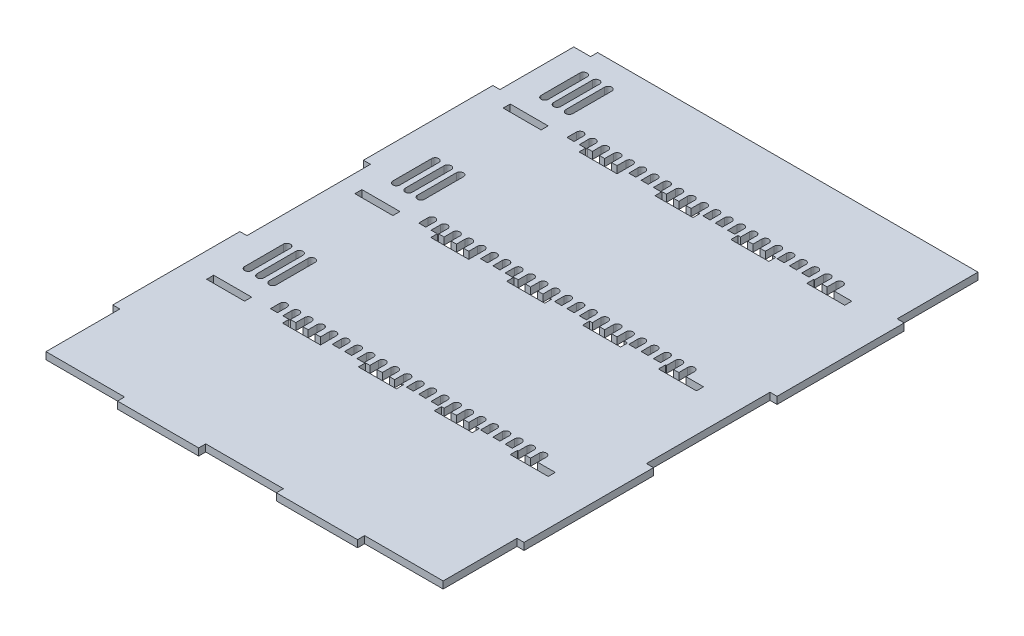
SolidWorks part; units mm, degrees
ref_plane "Front Plane" through (0, 0, 0) normal (0, 0, 1) x (1, 0, 0)
ref_plane "Top Plane" through (0, 0, 0) normal (0, 1, 0) x (1, 0, 0)
ref_plane "Right Plane" through (0, 0, 0) normal (1, 0, 0) x (0, 0, -1)
sketch "Sketch1" plane through (0, 0, 0) normal (0, 1, 0) x (1, 0, 0)
  line L1 (0, 0) -> (233, 0)
  line L2 (0, 0) -> (0, 307)
  line L3 (0, 307) -> (233, 307)
  line L4 (233, 0) -> (233, 307)
  dimension "D1" = 233
  dimension "D2" = 307
extrude "Boss-Extrude1" add sketch "Sketch1" along normal blind 4
sketch "Sketch2" plane through (0, 4, 0) normal (0, 1, 0) x (1, 0, 0)
  line L1 (0, 307) -> (4, 307)
  line L2 (0, 307) -> (0, 261.1667)
  line L3 (0, 261.1667) -> (4, 261.1667)
  line L4 (4, 307) -> (4, 261.1667)
  line L5 (0, 0) -> (4, 0)
  line L6 (0, 0) -> (0, 45.8333)
  line L7 (0, 45.8333) -> (4, 45.8333)
  line L8 (4, 0) -> (4, 45.8333)
  line L9 (233, 0) -> (233, 307) construction
  line L10 (0, 0) -> (233, 0) construction
  line L11 (4, 307) -> (13.5, 307)
  line L12 (4, 307) -> (4, 303)
  line L13 (4, 303) -> (13.5, 303)
  line L14 (13.5, 307) -> (13.5, 303)
  line L15 (94.5, 0) -> (94.5, 4)
  line L16 (4, 0) -> (48.5, 0)
  line L17 (4, 0) -> (4, 4)
  line L18 (4, 4) -> (48.5, 4)
  line L19 (48.5, 0) -> (48.5, 4)
  line L20 (94.5, 0) -> (138.5, 0)
  line L21 (138.5, 0) -> (138.5, 4)
  line L22 (94.5, 4) -> (138.5, 4)
  line L23 (184.5, 0) -> (184.5, 4)
  line L24 (184.5, 0) -> (229, 0)
  line L26 (184.5, 4) -> (229, 4)
  line L27 (229, 307) -> (229, 261.1667)
  line L28 (229, 307) -> (233, 307)
  line L29 (233, 307) -> (233, 261.1667)
  line L30 (229, 261.1667) -> (233, 261.1667)
  line L31 (229, 0) -> (229, 45.8333)
  line L32 (229, 0) -> (233, 0)
  line L33 (233, 0) -> (233, 45.8333)
  line L34 (229, 45.8333) -> (233, 45.8333)
  line M15 (0, 307) -> (0, 0)
  line M16 (0, 0) -> (233, 0)
  line M18 (233, 307) -> (0, 307)
  dimension "D1" = 45.8333
  dimension "D2" = 45.8333
  dimension "D3" = 4
  dimension "D4" = 9.5
  dimension "D5" = 4
  dimension "D6" = 44.5
  dimension "D7" = 4
  dimension "D10" = 46
  dimension "D8" = 44
  dimension "D11" = 46
  dimension "D9" = 2
extrude "Cut-Extrude1" cut sketch "Sketch2" against normal blind 4 contours L4 L3 M18 M15 | L14 L4 L13 M18 | L8 L7 M16 M15 | L26 L23 M16 | L17 L18 L19 L16 | L22 L21 L20 L15 | L31 L34 L33 L32 | L29 L30 L27 L28 region at (206.75, 4, -2) region at (2, 4, -22.9167) region at (2, 4, -284.0833) region at (8.75, 4, -305)
sketch "Sketch3" plane through (0, 0, 0) normal (0, -1, 0) x (1, 0, 0)
  line L7 (207.5, -253) -> (186, -253)
  line L8 (207.5, -253) -> (207.5, -257)
  line L9 (207.5, -257) -> (186, -257)
  line L10 (186, -253) -> (186, -257)
  line L12 (164.5, -253) -> (164.5, -257)
  line L13 (164.5, -253) -> (143, -253)
  line L14 (143, -253) -> (143, -257)
  line L15 (164.5, -257) -> (143, -257)
  line L16 (121.5, -253) -> (121.5, -257)
  line L17 (121.5, -253) -> (100, -253)
  line L18 (100, -253) -> (100, -257)
  line L19 (121.5, -257) -> (100, -257)
  line L20 (78.5, -253) -> (78.5, -257)
  line L21 (78.5, -253) -> (57, -253)
  line L22 (57, -253) -> (57, -257)
  line L23 (78.5, -257) -> (57, -257)
  line L24 (35.5, -253) -> (35.5, -257)
  line L25 (35.5, -253) -> (14, -253)
  line L26 (14, -253) -> (14, -257)
  line L27 (35.5, -257) -> (14, -257)
  line L106 (229, -307) -> (13.5, -307) construction
  line L107 (35.5, -169) -> (35.5, -173)
  line L108 (35.5, -173) -> (14, -173)
  line L109 (14, -169) -> (14, -173)
  line L110 (35.5, -169) -> (14, -169)
  line L111 (78.5, -169) -> (78.5, -173)
  line L112 (78.5, -173) -> (57, -173)
  line L113 (57, -169) -> (57, -173)
  line L114 (78.5, -169) -> (57, -169)
  line L115 (121.5, -169) -> (121.5, -173)
  line L116 (121.5, -173) -> (100, -173)
  line L117 (100, -169) -> (100, -173)
  line L118 (121.5, -169) -> (100, -169)
  line L119 (164.5, -169) -> (164.5, -173)
  line L120 (164.5, -173) -> (143, -173)
  line L121 (143, -169) -> (143, -173)
  line L122 (164.5, -169) -> (143, -169)
  line L123 (207.5, -169) -> (207.5, -173)
  line L124 (207.5, -169) -> (186, -169)
  line L125 (186, -169) -> (186, -173)
  line L126 (207.5, -173) -> (186, -173)
  line L127 (35.5, -85) -> (35.5, -89)
  line L128 (35.5, -89) -> (14, -89)
  line L129 (14, -85) -> (14, -89)
  line L130 (35.5, -85) -> (14, -85)
  line L131 (78.5, -85) -> (78.5, -89)
  line L132 (78.5, -89) -> (57, -89)
  line L133 (57, -85) -> (57, -89)
  line L134 (78.5, -85) -> (57, -85)
  line L135 (121.5, -85) -> (121.5, -89)
  line L136 (121.5, -89) -> (100, -89)
  line L137 (100, -85) -> (100, -89)
  line L138 (121.5, -85) -> (100, -85)
  line L139 (164.5, -85) -> (164.5, -89)
  line L140 (164.5, -89) -> (143, -89)
  line L141 (143, -85) -> (143, -89)
  line L142 (164.5, -85) -> (143, -85)
  line L143 (207.5, -85) -> (207.5, -89)
  line L144 (207.5, -85) -> (186, -85)
  line L145 (186, -85) -> (186, -89)
  line L146 (207.5, -89) -> (186, -89)
  dimension "D1" = 50
  dimension "D2" = 21.5
  dimension "D3" = 4
  dimension "D5" = 5
extrude "Cut-Extrude2" cut sketch "Sketch3" against normal blind 4
sketch "Sketch4" plane through (0, 4, 0) normal (0, 1, 0) x (1, 0, 0)
  line L0 (0, 261.1667) -> (0, 45.8333) construction
  line L1 (0, 187.8333) -> (4, 187.8333)
  line L2 (0, 187.8333) -> (0, 117.8333)
  line L3 (0, 117.8333) -> (4, 117.8333)
  line L4 (4, 187.8333) -> (4, 117.8333)
  line L5 (0, 45.8333) -> (4, 45.8333) construction
  point P6 (4, 152.8333)
  dimension "D1" = 4
  dimension "D2" = 70
  dimension "D3" = 107
extrude "Cut-Extrude3" cut sketch "Sketch4" against normal blind 4
sketch "Sketch5" plane through (0, 4, 0) normal (0, 1, 0) x (1, 0, 0)
  line L0 (233, 45.8333) -> (233, 261.1667) construction
  line L1 (233, 189.1667) -> (229, 189.1667)
  line L2 (233, 189.1667) -> (233, 119.1667)
  line L3 (233, 119.1667) -> (229, 119.1667)
  line L4 (229, 189.1667) -> (229, 119.1667)
  line L5 (229, 261.1667) -> (233, 261.1667) construction
  point P6 (233, 154.1667)
  dimension "D1" = 4
  dimension "D2" = 70
  dimension "D3" = 107
extrude "Cut-Extrude4" cut sketch "Sketch5" against normal blind 4
sketch "Sketch6" plane through (0, 4, 0) normal (0, 1, 0) x (1, 0, 0)
  line L0 (20.5, 292) -> (20.5, 270) construction
  line L1 (22.5, 292) -> (22.5, 270)
  line L2 (18.5, 292) -> (18.5, 270)
  line L4 (4, 303) -> (13.5, 303) construction
  line L11 (13.5, 307) -> (13.5, 303) construction
  line L17 (109.5011, 256.6579) -> (113.5011, 256.6579)
  line L18 (25.5402, 292) -> (25.5402, 270)
  line L21 (29.5402, 292) -> (29.5402, 270)
  line L22 (27.5402, 292) -> (27.5402, 270) construction
  line L23 (34.4609, 292) -> (34.4609, 270) construction
  line L24 (36.4609, 292) -> (36.4609, 270)
  line L25 (32.4609, 292) -> (32.4609, 270)
  line L26 (102.5011, 261.9985) -> (102.5011, 256.6579)
  line L27 (111.5011, 261.9985) -> (111.5011, 258.9985) construction
  line L29 (113.5011, 261.9985) -> (113.5011, 256.6579)
  line L30 (109.5011, 261.9985) -> (109.5011, 256.6579)
  line L31 (102.5011, 256.6579) -> (106.5011, 256.6579)
  line L32 (106.5011, 261.9985) -> (106.5011, 256.6579)
  line L33 (95.5011, 261.9985) -> (95.5011, 256.6579)
  line L34 (95.5011, 256.6579) -> (99.5011, 256.6579)
  line L35 (99.5011, 261.9985) -> (99.5011, 256.6579)
  line L36 (88.5011, 261.9985) -> (88.5011, 256.6579)
  line L37 (88.5011, 256.6579) -> (92.5011, 256.6579)
  line L38 (92.5011, 261.9985) -> (92.5011, 256.6579)
  line L39 (81.5011, 261.9985) -> (81.5011, 256.6579)
  line L40 (81.5011, 256.6579) -> (85.5011, 256.6579)
  line L41 (85.5011, 261.9985) -> (85.5011, 256.6579)
  line L42 (74.5011, 261.9985) -> (74.5011, 256.6579)
  line L43 (74.5011, 256.6579) -> (78.5011, 256.6579)
  line L44 (78.5011, 261.9985) -> (78.5011, 256.6579)
  line L45 (67.5011, 261.9985) -> (67.5011, 256.6579)
  line L46 (67.5011, 256.6579) -> (71.5011, 256.6579)
  line L47 (71.5011, 261.9985) -> (71.5011, 256.6579)
  line L48 (60.5011, 261.9985) -> (60.5011, 256.6579)
  line L49 (60.5011, 256.6579) -> (64.5011, 256.6579)
  line L50 (64.5011, 261.9985) -> (64.5011, 256.6579)
  line L51 (53.5011, 261.9985) -> (53.5011, 256.6579)
  line L52 (53.5011, 256.6579) -> (57.5011, 256.6579)
  line L53 (57.5011, 261.9985) -> (57.5011, 256.6579)
  line L54 (116.5011, 261.9985) -> (116.5011, 256.6579)
  line L55 (116.5011, 256.6579) -> (120.5011, 256.6579)
  line L56 (120.5011, 261.9985) -> (120.5011, 256.6579)
  line L57 (123.5011, 261.9985) -> (123.5011, 256.6579)
  line L58 (123.5011, 256.6579) -> (127.5011, 256.6579)
  line L59 (127.5011, 261.9985) -> (127.5011, 256.6579)
  line L60 (130.5011, 261.9985) -> (130.5011, 256.6579)
  line L61 (130.5011, 256.6579) -> (134.5011, 256.6579)
  line L62 (134.5011, 261.9985) -> (134.5011, 256.6579)
  line L63 (137.5011, 261.9985) -> (137.5011, 256.6579)
  line L64 (137.5011, 256.6579) -> (141.5011, 256.6579)
  line L65 (141.5011, 261.9985) -> (141.5011, 256.6579)
  line L66 (144.5011, 261.9985) -> (144.5011, 256.6579)
  line L67 (144.5011, 256.6579) -> (148.5011, 256.6579)
  line L68 (148.5011, 261.9985) -> (148.5011, 256.6579)
  line L69 (151.5011, 261.9985) -> (151.5011, 256.6579)
  line L70 (151.5011, 256.6579) -> (155.5011, 256.6579)
  line L71 (155.5011, 261.9985) -> (155.5011, 256.6579)
  line L72 (158.5011, 261.9985) -> (158.5011, 256.6579)
  line L73 (158.5011, 256.6579) -> (162.5011, 256.6579)
  line L74 (162.5011, 261.9985) -> (162.5011, 256.6579)
  line L75 (165.5011, 261.9985) -> (165.5011, 256.6579)
  line L76 (165.5011, 256.6579) -> (169.5011, 256.6579)
  line L77 (169.5011, 261.9985) -> (169.5011, 256.6579)
  line L78 (172.5011, 261.9985) -> (172.5011, 256.6579)
  line L79 (172.5011, 256.6579) -> (176.5011, 256.6579)
  line L80 (176.5011, 261.9985) -> (176.5011, 256.6579)
  line L81 (179.5011, 261.9985) -> (179.5011, 256.6579)
  line L82 (179.5011, 256.6579) -> (183.5011, 256.6579)
  line L83 (183.5011, 261.9985) -> (183.5011, 256.6579)
  line L84 (186.5011, 261.9985) -> (186.5011, 256.6579)
  line L85 (186.5011, 256.6579) -> (190.5011, 256.6579)
  line L86 (190.5011, 261.9985) -> (190.5011, 256.6579)
  line L87 (46.5011, 261.9985) -> (46.5011, 256.6579)
  line L88 (46.5011, 256.6579) -> (50.5011, 256.6579)
  line L89 (50.5011, 261.9985) -> (50.5011, 256.6579)
  line L90 (193.5011, 261.9985) -> (193.5011, 256.6579)
  line L91 (193.5011, 256.6579) -> (197.5011, 256.6579)
  line L92 (197.5011, 261.9985) -> (197.5011, 256.6579)
  arc A0 (22.5, 292) -> (18.5, 292) centre (20.5, 292) ccw
  arc A1 (18.5, 270) -> (22.5, 270) centre (20.5, 270) ccw
  arc A14 (29.5402, 292) -> (25.5402, 292) centre (27.5402, 292) ccw
  arc A15 (25.5402, 270) -> (29.5402, 270) centre (27.5402, 270) ccw
  arc A16 (36.4609, 292) -> (32.4609, 292) centre (34.4609, 292) ccw
  arc A17 (32.4609, 270) -> (36.4609, 270) centre (34.4609, 270) ccw
  arc A18 (113.5011, 261.9985) -> (109.5011, 261.9985) centre (111.5011, 261.9985) ccw
  arc A20 (106.5011, 261.9985) -> (102.5011, 261.9985) centre (104.5011, 261.9985) ccw
  arc A21 (99.5011, 261.9985) -> (95.5011, 261.9985) centre (97.5011, 261.9985) ccw
  arc A22 (92.5011, 261.9985) -> (88.5011, 261.9985) centre (90.5011, 261.9985) ccw
  arc A23 (85.5011, 261.9985) -> (81.5011, 261.9985) centre (83.5011, 261.9985) ccw
  arc A24 (78.5011, 261.9985) -> (74.5011, 261.9985) centre (76.5011, 261.9985) ccw
  arc A25 (71.5011, 261.9985) -> (67.5011, 261.9985) centre (69.5011, 261.9985) ccw
  arc A26 (64.5011, 261.9985) -> (60.5011, 261.9985) centre (62.5011, 261.9985) ccw
  arc A27 (57.5011, 261.9985) -> (53.5011, 261.9985) centre (55.5011, 261.9985) ccw
  arc A28 (120.5011, 261.9985) -> (116.5011, 261.9985) centre (118.5011, 261.9985) ccw
  arc A29 (127.5011, 261.9985) -> (123.5011, 261.9985) centre (125.5011, 261.9985) ccw
  arc A30 (134.5011, 261.9985) -> (130.5011, 261.9985) centre (132.5011, 261.9985) ccw
  arc A31 (141.5011, 261.9985) -> (137.5011, 261.9985) centre (139.5011, 261.9985) ccw
  arc A32 (148.5011, 261.9985) -> (144.5011, 261.9985) centre (146.5011, 261.9985) ccw
  arc A33 (155.5011, 261.9985) -> (151.5011, 261.9985) centre (153.5011, 261.9985) ccw
  arc A34 (162.5011, 261.9985) -> (158.5011, 261.9985) centre (160.5011, 261.9985) ccw
  arc A35 (169.5011, 261.9985) -> (165.5011, 261.9985) centre (167.5011, 261.9985) ccw
  arc A36 (176.5011, 261.9985) -> (172.5011, 261.9985) centre (174.5011, 261.9985) ccw
  arc A37 (183.5011, 261.9985) -> (179.5011, 261.9985) centre (181.5011, 261.9985) ccw
  arc A38 (190.5011, 261.9985) -> (186.5011, 261.9985) centre (188.5011, 261.9985) ccw
  arc A39 (50.5011, 261.9985) -> (46.5011, 261.9985) centre (48.5011, 261.9985) ccw
  arc A40 (197.5011, 261.9985) -> (193.5011, 261.9985) centre (195.5011, 261.9985) ccw
  point P2 (20.5, 281)
  point P14 (111.5011, 260.4985)
  point P16 (27.5402, 281)
  point P23 (34.4609, 281)
  dimension "D2" = 4
  dimension "D3" = 2
  dimension "D4" = 2
  dimension "D6" = 2
  dimension "D8" = 4
  dimension "D10" = 7
  dimension "D11" = 8.0015
  dimension "D7" = 22
  dimension "D9" = 11
  dimension "D5" = 2
  dimension "D13" = 9
  dimension "D14" = 12
extrude "Cut-Extrude5" cut sketch "Sketch6" against normal blind 4
pattern_linear "LPattern1" count 3 spacing 84 along (0, 0, 1) of "Cut-Extrude5"
equation "\"Dikte\"= 4"
equation "\"D1@Sketch1\"=\"Dikte\"*2+225"
equation "\"D2@Sketch1\"=135+\"Dikte\" + 34*2 + 50*2"
equation "\"D1@Sketch2\"=139/3-\"Tolerantie\""
equation "\"D2@Sketch2\"=\"D1@Sketch2\""
equation "\"D5@Sketch2\"=\"Dikte\""
equation "\"Tolerantie\"= 0.5"
equation "\"D6@Sketch2\"=45-\"Tolerantie\""
equation "\"D10@Sketch2\"=45+2*\"Tolerantie\""
equation "\"D8@Sketch2\"=45-2*\"Tolerantie\""
equation "\"D11@Sketch2\"=\"D10@Sketch2\""
equation "\"D4@Sketch2\"=10-\"Tolerantie\""
